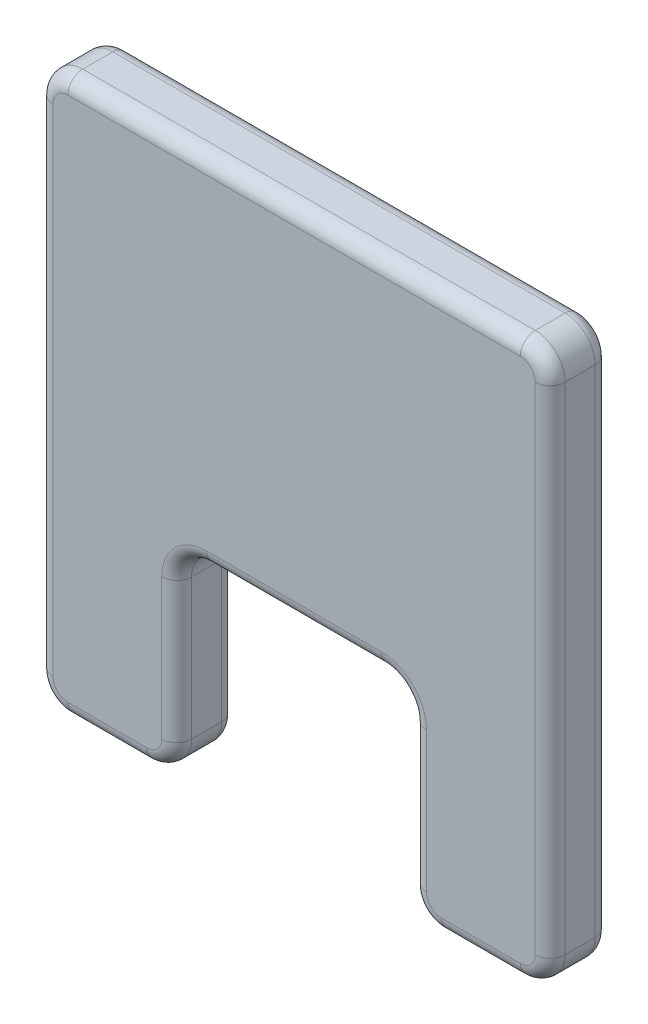
SolidWorks part; units mm, degrees
material "Polyurethane Foam Flexible"
ref_plane "Front Plane" through (0, 0, 0) normal (0, 0, 1) x (1, 0, 0)
ref_plane "Top Plane" through (0, 0, 0) normal (0, 1, 0) x (1, 0, 0)
ref_plane "Right Plane" through (0, 0, 0) normal (1, 0, 0) x (0, 0, -1)
sketch "Sketch1" plane through (0, 0, 0) normal (0, 0, 1) x (1, 0, 0)
  line L0 (-93.2955, 339.5666) -> (-93.2955, -223.9129) construction
  line L1 (-93.2955, 241.2246) -> (341.3045, 241.2246)
  line L2 (-93.2955, 241.2246) -> (-93.2955, -230.2629)
  line L3 (-93.2955, -230.2629) -> (24.3822, -230.2629)
  line L4 (341.3045, 241.2246) -> (341.3045, -230.2629)
  line L5 (223.6267, -230.2629) -> (341.3045, -230.2629)
  line L7 (24.3822, -230.2629) -> (24.3822, -60.2629)
  line L8 (24.3822, -60.2629) -> (223.6267, -60.2629)
  line L9 (223.6267, -230.2629) -> (223.6267, -60.2629)
  line L10 (24.3822, -223.9129) -> (24.3822, -60.2629) construction
  line L11 (16.7045, -230.2629) -> (-93.2955, -230.2629) construction
  line L12 (341.3045, -223.9129) -> (341.3045, 339.5666) construction
  dimension "D1" = 471.4875
extrude "Boss-Extrude1" add sketch "Sketch1" along normal blind 50.8
fillet "Fillet1" radius 25.4 8 edges at (24.3822, -230.2629, 25.4) (-93.2955, -230.2629, 25.4) (-93.2955, 241.2246, 25.4) (341.3045, 241.2246, 25.4) (341.3045, -230.2629, 25.4) (223.6267, -230.2629, 25.4) (223.6267, -60.2629, 25.4) (24.3822, -60.2629, 25.4)
fillet "Fillet2" radius 12.7 32 edges at (31.8217, -67.7023, 0) (124.0045, -60.2629, 0) (216.1872, -67.7023, 0) (223.6267, -145.2629, 0) (231.0662, -222.8234, 0) (282.4656, -230.2629, 0) (333.865, -222.8234, 0) (341.3045, 5.4809, 0) (333.865, 233.7852, 0) (124.0045, 241.2246, 0) (-85.856, 233.7852, 0) (-93.2955, 5.4809, 0) (-85.856, -222.8234, 0) (-34.4566, -230.2629, 0) (16.9428, -222.8234, 0) (24.3822, -145.2629, 0) (-85.856, -222.8234, 50.8) (-93.2955, 5.4809, 50.8) (-85.856, 233.7852, 50.8) (124.0045, 241.2246, 50.8) (333.865, 233.7852, 50.8) (341.3045, 5.4809, 50.8) (333.865, -222.8234, 50.8) (282.4656, -230.2629, 50.8) (231.0662, -222.8234, 50.8) (223.6267, -145.2629, 50.8) (216.1872, -67.7023, 50.8) (124.0045, -60.2629, 50.8) (31.8217, -67.7023, 50.8) (24.3822, -145.2629, 50.8) (16.9428, -222.8234, 50.8) (-34.4566, -230.2629, 50.8)
